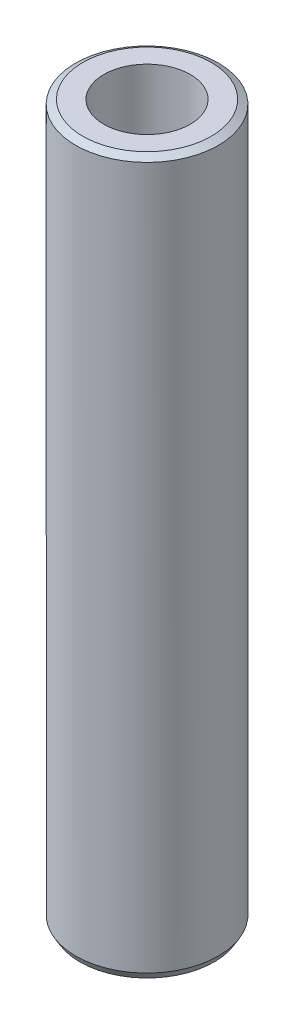
SolidWorks part; units mm, degrees
ref_plane "Front Plane" through (0, 0, 0) normal (0, 0, 1) x (1, 0, 0)
ref_plane "Top Plane" through (0, 0, 0) normal (0, 1, 0) x (1, 0, 0)
ref_plane "Right Plane" through (0, 0, 0) normal (1, 0, 0) x (0, 0, -1)
sketch "Sketch1" plane through (0, 0, 0) normal (0, 1, 0) x (1, 0, 0)
  circle A0 centre (0, 0) radius 60
  dimension "SHAFT_OD" = 120
extrude "Boss-Extrude1" add sketch "Sketch1" along normal blind 600
sketch "Sketch2" plane through (0, 0, 0) normal (0, 1, 0) x (1, 0, 0)
  circle A0 centre (0, 0) radius 36.3198
  dimension "BORE_D" = 72.6396
extrude "Cut-Extrude1" cut sketch "Sketch2" along normal through all
chamfer "Chamfer1" distance 3.5164 angle 60 2 edges at (0, 600, 60) (0, 0, 60) first distance on face at (0, 600, 60) first distance on face at (0, 0, 36.3198)
